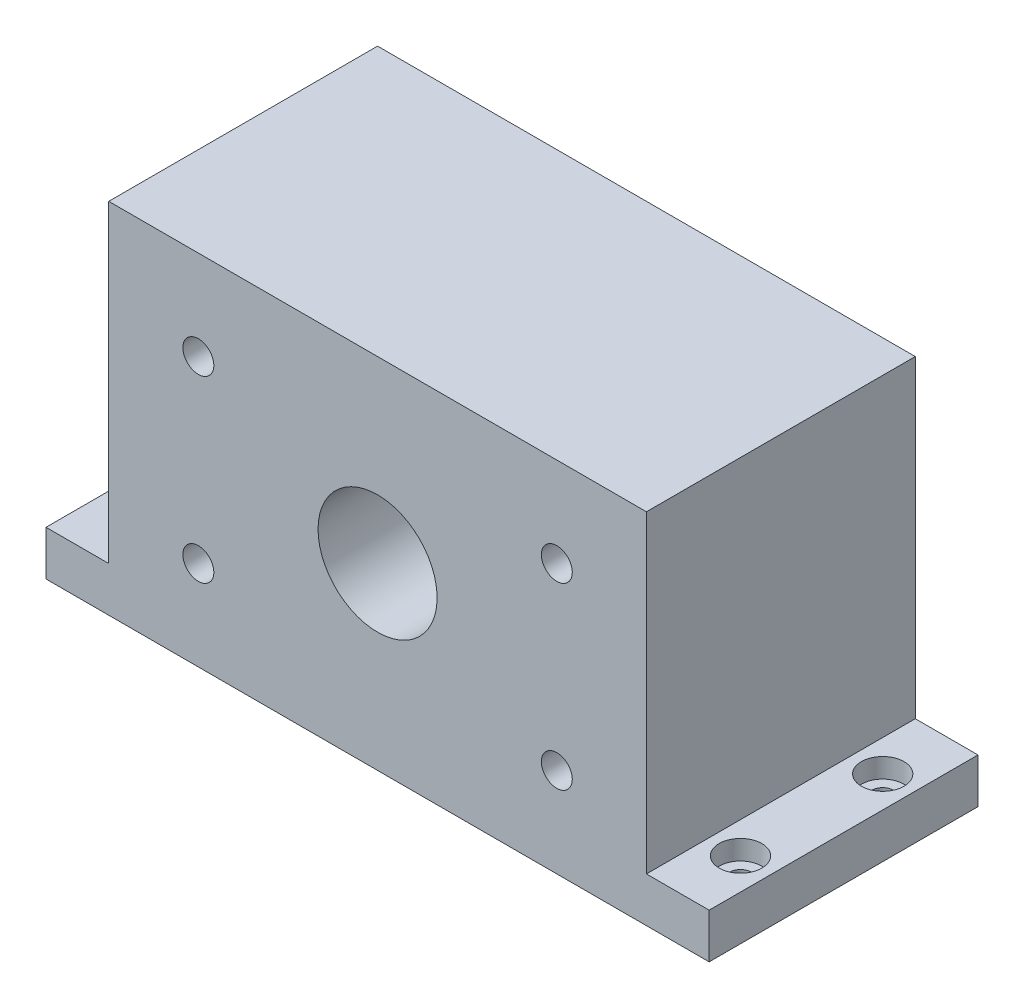
SolidWorks part; units mm, degrees
ref_plane "Front Plane" through (0, 0, 0) normal (0, 0, 1) x (1, 0, 0)
ref_plane "Top Plane" through (0, 0, 0) normal (0, 1, 0) x (1, 0, 0)
ref_plane "Right Plane" through (0, 0, 0) normal (1, 0, 0) x (0, 0, -1)
sketch "Sketch5" plane through (0, 0, 0) normal (0, 1, 0) x (1, 0, 0)
  line L1 (-30, 15) -> (30, 15)
  line L2 (-30, 15) -> (-30, -15)
  line L3 (-30, -15) -> (30, -15)
  line L4 (30, 15) -> (30, -15)
  line L5 (-30, 15) -> (30, -15) construction
  line L6 (-30, -15) -> (30, 15) construction
  point P0 (0, 0)
  dimension "D1" = 30
  dimension "D2" = 60
extrude "Boss-Extrude3" add sketch "Sketch5" along normal blind 40
sketch "Sketch6" plane through (0, 0, 15) normal (0, 0, 1) x (1, 0, 0)
  line L0 (0, 20) -> (-20, 20) construction
  line L3 (-25, 35) -> (25, 35)
  line L4 (-25, 35) -> (-25, 5)
  line L5 (-25, 5) -> (25, 5)
  line L6 (25, 35) -> (25, 5)
  line L7 (-25, 35) -> (25, 5) construction
  line L8 (-25, 5) -> (25, 35) construction
  line L10 (-20, 20) -> (-20, 30) construction
  line L12 (0, 20) -> (20, 20) construction
  line L13 (20, 20) -> (20, 10) construction
  line L14 (-20, 20) -> (-20, 10) construction
  line L15 (20, 20) -> (20, 30) construction
  line L16 (-30, 40) -> (-30, 0) construction
  line L17 (-30, 0) -> (30, 0) construction
  line L18 (-30, 40) -> (30, 40) construction
  point P8 (0, 20)
  dimension "D1" = 50
  dimension "D2" = 30
sketch "Sketch7" plane through (0, 0, -15) normal (0, 0, -1) x (-1, 0, 0)
  line L3 (-20, 10) -> (20, 10)
  line L4 (-20, 10) -> (-20, 30)
  line L5 (-20, 30) -> (20, 30)
  line L6 (20, 10) -> (20, 30)
  line L7 (-20, 10) -> (20, 30) construction
  line L8 (-20, 30) -> (20, 10) construction
  point P8 (0, 20)
  dimension "D1" = 20
  dimension "D2" = 40
extrude "Cut-Extrude1" cut sketch "Sketch7" against normal blind 15
fillet "Fillet1" radius 3 1 edges at (20, 10, -7.5)
fillet "Fillet2" radius 3 1 edges at (-20, 10, -7.5)
fillet "Fillet3" radius 3 1 edges at (-20, 30, -7.5)
fillet "Fillet4" radius 3 1 edges at (20, 30, -7.5)
sketch "Sketch8" plane through (0, 10, 0) normal (0, 1, 0) x (1, 0, 0)
  line L0 (0, 15) -> (0, 0) construction
  line L1 (17, 15) -> (-17, 15) construction
  dimension "D1" = 15
sketch "Sketch9" plane through (-30, 0, 0) normal (-1, 0, 0) x (0, 0, 1)
  line L0 (15, 40) -> (15, 0) construction
  line L1 (-15, 0) -> (15, 0)
  line L2 (-15, 0) -> (-15, 5)
  line L3 (-15, 5) -> (15, 5)
  line L4 (15, 0) -> (15, 5)
extrude "Boss-Extrude4" add sketch "Sketch9" along normal blind 7
sketch "Sketch10" plane through (30, 0, 0) normal (1, 0, 0) x (0, 0, -1)
  line L0 (15, 40) -> (15, 0) construction
  line L1 (-15, 0) -> (15, 0)
  line L2 (-15, 0) -> (-15, 5)
  line L3 (-15, 5) -> (15, 5)
  line L4 (15, 0) -> (15, 5)
extrude "Boss-Extrude5" add sketch "Sketch10" along normal blind 7
sketch "Sketch11" plane through (-30, 0, 0) normal (-1, 0, 0) x (0, 0, 1)
  line L0 (-15, 40) -> (0, 40) construction
  line L1 (-15, 40) -> (15, 40) construction
  line L2 (0, 40) -> (0, 5) construction
  line L3 (15, 5) -> (-15, 5) construction
  line L4 (0, 40) -> (-15, 5) construction
sketch "Sketch12" plane through (-30, 0, 0) normal (-1, 0, 0) x (0, 0, 1)
  circle A0 centre (-7.5315, 22.7105) radius 2
extrude "Cut-Extrude2" cut sketch "Sketch12" against normal blind 10
sketch "Sketch13" plane through (0, 0, 0) normal (0, -1, 0) x (-1, 0, 0)
  line L0 (-37, 15) -> (37, -15) construction
  line L1 (-37, -15) -> (37, 15) construction
  line L3 (-32, 10) -> (32, 10)
  line L4 (-32, 10) -> (-32, -10)
  line L5 (-32, -10) -> (32, -10)
  line L6 (32, 10) -> (32, -10)
  line L7 (-32, 10) -> (32, -10) construction
  line L8 (-32, -10) -> (32, 10) construction
  point P8 (0, 0)
  dimension "D1" = 64
  dimension "D2" = 20
extrude "Cut-Extrude3" cut sketch "Sketch13" against normal blind 1.5
sketch "Sketch14" plane through (0, 0, -15) normal (0, 0, -1) x (-1, 0, 0)
sketch "Sketch16" plane through (0, 5, 0) normal (0, 1, 0) x (1, 0, 0)
  line L3 (37, -15) -> (30, -15) construction
  line L6 (33.5, -15) -> (33.5, -8) construction
  line L7 (33.5004, 14.8485) -> (33.5184, 7.8485) construction
  point P11 (37, -15)
hole_wizard "CBORE for #2 Socket Head Cap Screw1" positions "3DSketch2" profile "Sketch17" counterbore size "#2" standard "ANSI Inch"
sketch3d "3DSketch2"
  point P0 (33.5, 5, 8)
  point P3 (33.5184, 5, -7.8485)
sketch "Sketch17" plane through (33.5, 5, 8) normal (1, 0, 0) x (0, 0, 1)
  line L0 (0, 0) -> (0, 15.7326)
  line L1 (0, 15.7326) -> (1.2192, 15)
  line L2 (1.2192, 15) -> (1.2192, 2.1844)
  line L3 (1.2192, 2.1844) -> (2.3812, 2.1844)
  line L4 (2.3812, 2.1844) -> (2.3812, 0)
  line L5 (2.3812, 0) -> (0, 0)
  line L10 (0, 15.7326) -> (-1.2192, 15) construction
  line L11 (0, -6.35) -> (0, 107.95) construction
  dimension "Hole Dia." = 2.4384
  dimension "Hole Depth" = 15
  dimension "C'Bore Dia." = 4.7625
  dimension "C'Bore Depth" = 2.1844
  dimension "Drill Angle" = 118
sketch "Sketch18" plane through (0, 5, 0) normal (0, 1, 0) x (1, 0, 0)
  line L2 (-33.5, -15) -> (-33.5, -8) construction
  line L3 (-37, -15) -> (-30, -15) construction
  line L4 (-33.5, 15) -> (-33.5, 8) construction
  line L5 (-37, 15) -> (-30, 15) construction
sketch "Sketch22" plane through (0, 0, -15) normal (0, 0, -1) x (-1, 0, 0)
  line L0 (25, 4) -> (25, 36) construction
  line L1 (-37, 0) -> (37, 0) construction
  line L3 (-30, 40) -> (-30, 0) construction
  line L4 (-25, 20) -> (-25, 36) construction
  line L7 (-25, 20) -> (-25, 4) construction
  line L8 (-25, 36) -> (25, 36) construction
  line L9 (25, 36) -> (25, 4) construction
hole_wizard "#2-56 Tapped Hole2" positions "3DSketch4" profile "Sketch23" tap size "#2-56" standard "ANSI Inch"
sketch3d "3DSketch4"
  point P0 (25, 36, -15)
  point P3 (25, 4, -15)
  point P6 (-25, 4, -15)
sketch "Sketch23" plane through (25, 36, -15) normal (1, 0, 0) x (0, 1, 0)
  line L0 (0, 0) -> (0, 15.5342)
  line L1 (0, 15.5342) -> (0.889, 15)
  line L2 (0.889, 15) -> (0.889, 0)
  line L5 (0.889, 0) -> (0, 0)
  line L10 (0, 15.5342) -> (-0.889, 15) construction
  line L11 (0, -6.35) -> (0, 107.95) construction
  dimension "Tap Drill Dia." = 1.778
  dimension "Tap Drill Depth" = 15
  dimension "Drill Angle" = 118
cosmetic thread "Hole Thread1" parameters "D1"=12, "D2"=2.1844
cosmetic thread "Hole Thread2" parameters "D1"=12, "D2"=2.1844
cosmetic thread "Hole Thread3" parameters "D1"=12, "D2"=2.1844
hole_wizard "#2-56 Tapped Hole3" positions "3DSketch5" profile "Sketch24" tap size "#2-56" standard "ANSI Inch"
sketch3d "3DSketch5"
  point P0 (-25, 36, -15)
sketch "Sketch24" plane through (-25, 36, -15) normal (1, 0, 0) x (0, 1, 0)
  line L0 (0, 0) -> (0, 15.5342)
  line L1 (0, 15.5342) -> (0.889, 15)
  line L2 (0.889, 15) -> (0.889, 0)
  line L5 (0.889, 0) -> (0, 0)
  line L10 (0, 15.5342) -> (-0.889, 15) construction
  line L11 (0, -6.35) -> (0, 107.95) construction
  dimension "Tap Drill Dia." = 1.778
  dimension "Tap Drill Depth" = 15
  dimension "Drill Angle" = 118
cosmetic thread "Hole Thread4" parameters "D1"=12, "D2"=2.1844
hole_wizard "CBORE for #2 Socket Head Cap Screw3" positions "Sketch25" profile "Sketch26" counterbore size "#2" standard "ANSI Inch"
sketch "Sketch25" plane through (0, 5, 0) normal (0, 1, 0) x (1, 0, 0)
  point P0 (-33.5, 8)
  point P3 (-33.5, -8)
sketch "Sketch26" plane through (-33.5, 5, -8) normal (1, 0, 0) x (0, 0, 1)
  line L0 (0, 0) -> (0, 15.7326)
  line L1 (0, 15.7326) -> (1.2192, 15)
  line L2 (1.2192, 15) -> (1.2192, 2.1844)
  line L3 (1.2192, 2.1844) -> (2.3812, 2.1844)
  line L4 (2.3812, 2.1844) -> (2.3812, 0)
  line L5 (2.3812, 0) -> (0, 0)
  line L10 (0, 15.7326) -> (-1.2192, 15) construction
  line L11 (0, -6.35) -> (0, 107.95) construction
  dimension "Hole Dia." = 2.4384
  dimension "Hole Depth" = 15
  dimension "C'Bore Dia." = 4.7625
  dimension "C'Bore Depth" = 2.1844
  dimension "Drill Angle" = 118
hole_wizard "#8-32 Tapped Hole1" positions "Sketch27" profile "Sketch28" tap size "#8-32" standard "ANSI Inch"
sketch "Sketch27" plane through (0, 0, 15) normal (0, 0, 1) x (1, 0, 0)
  point P0 (-20, 30)
  point P3 (-20, 10)
  point P6 (20, 10)
  point P9 (20, 30)
sketch "Sketch28" plane through (-20, 30, 15) normal (1, 0, 0) x (0, -1, 0)
  line L0 (0, 0) -> (0, 12.0378)
  line L1 (0, 12.0378) -> (1.7272, 11)
  line L2 (1.7272, 11) -> (1.7272, 0)
  line L5 (1.7272, 0) -> (0, 0)
  line L10 (0, 12.0378) -> (-1.7272, 11) construction
  line L11 (0, -6.35) -> (0, 107.95) construction
  dimension "Tap Drill Dia." = 3.4544
  dimension "Tap Drill Depth" = 11
  dimension "Drill Angle" = 118
cosmetic thread "Hole Thread5" parameters "D1"=8.33, "D2"=4.1656
cosmetic thread "Hole Thread6" parameters "D1"=8.33, "D2"=4.1656
cosmetic thread "Hole Thread7" parameters "D1"=8.33, "D2"=4.1656
cosmetic thread "Hole Thread8" parameters "D1"=8.33, "D2"=4.1656
sketch "Sketch29" plane through (0, 0, 0) normal (0, 0, -1) x (-1, 0, 0)
  line L0 (-20, 27) -> (-20, 13) construction
sketch "Sketch30" plane through (0, 0, 0) normal (0, 0, -1) x (-1, 0, 0)
  line L0 (20, 27) -> (20, 13) construction
  line L1 (-20, 27) -> (-20, 20) construction
  line L2 (-20, 27) -> (20, 13) construction
  line L3 (-20, 27) -> (-20, 13) construction
  line L4 (0, 20) -> (-12.5, 20) construction
  line L5 (0, 20) -> (12.5, 20) construction
  line L6 (0, 20) -> (-20, 20) construction
  circle A0 centre (-12.5, 20) radius 1.5
  circle A1 centre (12.5, 20) radius 3
sketch "Sketch32" plane through (0, 0, 0) normal (0, 0, -1) x (-1, 0, 0)
  line L0 (0, 10) -> (0, 20) construction
  line L1 (-17, 10) -> (17, 10) construction
  line L2 (25, 35) -> (-25, 5) construction
  line L3 (0, 20) -> (-20, 20) construction
  line L4 (-20, 27) -> (-20, 13) construction
hole_wizard "0.535-40 Tapped Hole1" positions "3DSketch6" profile "Sketch33" tap size "0.535-40" standard "ANSI Inch" end condition through all
sketch3d "3DSketch6"
  point P0 (0, 20, 0)
sketch "Sketch33" plane through (0, 20, 0) normal (1, 0, 0) x (0, 1, 0)
  line L0 (0, 0) -> (0, 15)
  line L1 (0, 15) -> (6.6421, 15)
  line L2 (6.6421, 15) -> (6.6421, 0)
  line L5 (6.6421, 0) -> (0, 0)
  line L11 (0, -6.35) -> (0, 107.95) construction
  dimension "Thru Tap Drill Dia." = 13.2842
  dimension "Thru Tap Drill Depth" = 15
cosmetic thread "Hole Thread9" parameters "D2"=13.589
extrude "Cut-Extrude5" cut sketch "Sketch30" against normal blind 10 contours A0 | A1
